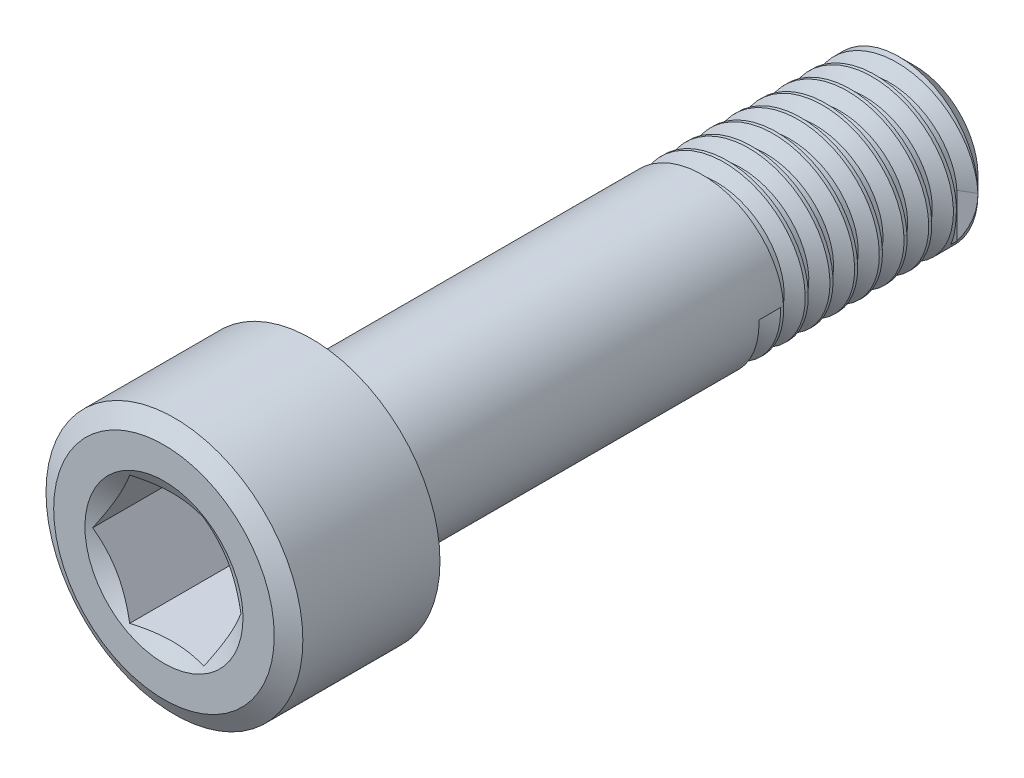
SolidWorks part; units mm, degrees
material "Stainless Steel (ferritic)"
ref_plane "Front Plane" through (0, 0, 0) normal (0, 0, 1) x (1, 0, 0)
ref_plane "Top Plane" through (0, 0, 0) normal (0, 1, 0) x (1, 0, 0)
ref_plane "Right Plane" through (0, 0, 0) normal (1, 0, 0) x (0, 0, -1)
sketch "Sketch1" plane through (0, 0, 0) normal (1, 0, 0) x (0, 0, -1)
  line L0 (0, 0) -> (66.2642, 0) construction
  line L1 (0, 0) -> (0, 5.582)
  line L2 (0, 5.582) -> (0.53, 6.5)
  line L3 (0.53, 6.5) -> (7.47, 6.5)
  line L4 (7.47, 6.5) -> (8, 5.582)
  line L5 (8, 5.582) -> (8, 4)
  line L6 (8, 4) -> (38, 4)
  line L7 (38, 4) -> (38, 0)
  line L8 (38, 0) -> (0, 0)
  dimension "D1" = 4
  dimension "D2" = 30
  dimension "D3" = 8
  dimension "D4" = 6.5
  dimension "D5" = 30
  dimension "D6" = 30
  dimension "D7" = 0.53
  dimension "D8" = 0.53
revolve "Revolve1" add sketch "Sketch1" angle 360 about L0
chamfer "Chamfer1" distance 0.8 angle 45 1 edges at (4, 0, -38)
sketch "Sketch2" plane through (0, 0, 0) normal (0, 0, 1) x (1, 0, 0)
  line L1 (-1.8764, -3.25) -> (1.8764, -3.25)
  line L2 (1.8764, -3.25) -> (3.7528, 0)
  line L3 (3.7528, 0) -> (1.8764, 3.25)
  line L4 (1.8764, 3.25) -> (-1.8764, 3.25)
  line L5 (-1.8764, 3.25) -> (-3.7528, 0)
  line L6 (-3.7528, 0) -> (-1.8764, -3.25)
  circle A0 centre (0, 0) radius 3.25 construction
  dimension "D1" = 6.5
extrude "Cut-Extrude1" cut sketch "Sketch2" against normal blind 6
sketch "Sketch3" plane through (0, 0, 0) normal (1, 0, 0) x (0, 0, -1)
  line L0 (0, 0) -> (40.9537, 0) construction
  line L1 (0, 0) -> (0, 4)
  line L2 (0, 5.582) -> (0, -5.582) construction
  line L3 (0, 4) -> (2.3094, 0)
  line L4 (2.3094, 0) -> (0, 0)
  line L5 (6, 3.25) -> (6, 0)
  line L6 (6, 0) -> (7.8764, 0)
  line L7 (7.8764, 0) -> (6, 3.25)
  dimension "D1" = 30
  dimension "D2" = 30
  dimension "D3" = 4
revolve "Cut-Revolve1" cut sketch "Sketch3" angle 360 about L0
thread "Thread1" pitch 1.25 method cut profile "Thread Profile2" start angle 0, offset 0, length 10, pitch 1.25, diameter 8
ref_plane "Plane2" through (4, 0, -37.2) normal (0, -1, 0) x (1, 0, 0)
sketch "Thread Profile2" plane through (4, 0, -37.2) normal (0, -1, 0) x (1, 0, 0)
  line L0 (0, 0) -> (0, 1.25) construction
  line L11 (0, 0) -> (0, 1.0937)
  line L12 (0, 1.0937) -> (-0.6766, 0.7031)
  line L13 (-0.6766, 0.7031) -> (-0.6766, 0.3906)
  line L15 (-0.6766, 0.3906) -> (0, 0)
  line L17 (-0.6766, 0.5469) -> (0, 0.5469) construction
  point P2 (0, 0)
  dimension "Pitch" = 1.25
  dimension "Profile_Angle" = 60
  dimension "Profile_Land" = 0.3125
  dimension "Profile_Height" = 0.6766
sketch "Sketch20" plane through (0, 0, 0) normal (0, 1, 0) x (1, 0, 0)
  line L4 (4, 37.2) -> (3.3234, 36.8094)
  line L5 (3.3234, 36.8094) -> (3.3234, 36.4969)
  line L6 (3.3234, 36.4969) -> (4, 36.1063)
  line L7 (4, 36.1063) -> (4, 37.2)
  line L8 (4, 37.2) -> (3.3234, 36.8094)
  line L9 (3.3234, 36.8094) -> (3.3234, 36.4969)
  line L10 (3.3234, 36.4969) -> (4, 36.1063)
  line L11 (4, 36.1063) -> (4, 37.2)
  dimension "D1" = 0
extrude "Cut-Extrude2" cut sketch "Sketch20" against normal blind 10
